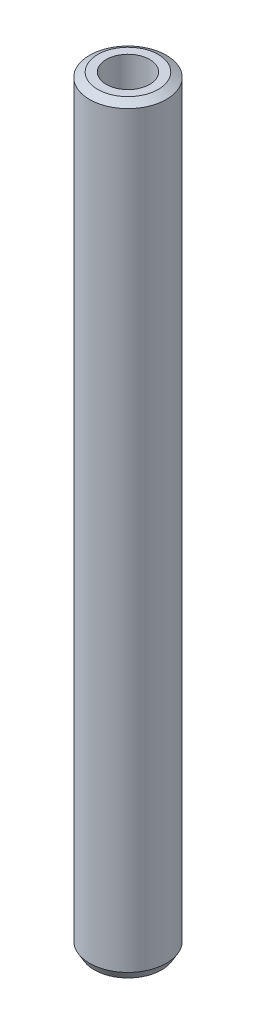
SolidWorks part; units mm, degrees
ref_plane "Front Plane" through (0, 0, 0) normal (0, 0, 1) x (1, 0, 0)
ref_plane "Top Plane" through (0, 0, 0) normal (0, 1, 0) x (1, 0, 0)
ref_plane "Right Plane" through (0, 0, 0) normal (1, 0, 0) x (0, 0, -1)
sketch "Sketch1" plane through (0, 0, 0) normal (0, 1, 0) x (1, 0, 0)
  circle A0 centre (0, 0) radius 27.5
  dimension "SHAFT_OD" = 55
extrude "Boss-Extrude1" add sketch "Sketch1" along normal blind 545.214
sketch "Sketch2" plane through (0, 0, 0) normal (0, 1, 0) x (1, 0, 0)
  circle A0 centre (0, 0) radius 15.5354
  dimension "BORE_D" = 31.0707
extrude "Cut-Extrude1" cut sketch "Sketch2" along normal through all
chamfer "Chamfer1" distance 3.3496 angle 60 2 edges at (0, 545.214, 27.5) (0, 0, 27.5) first distance on face at (0, 545.214, 27.5) first distance on face at (0, 0, 15.5354)
